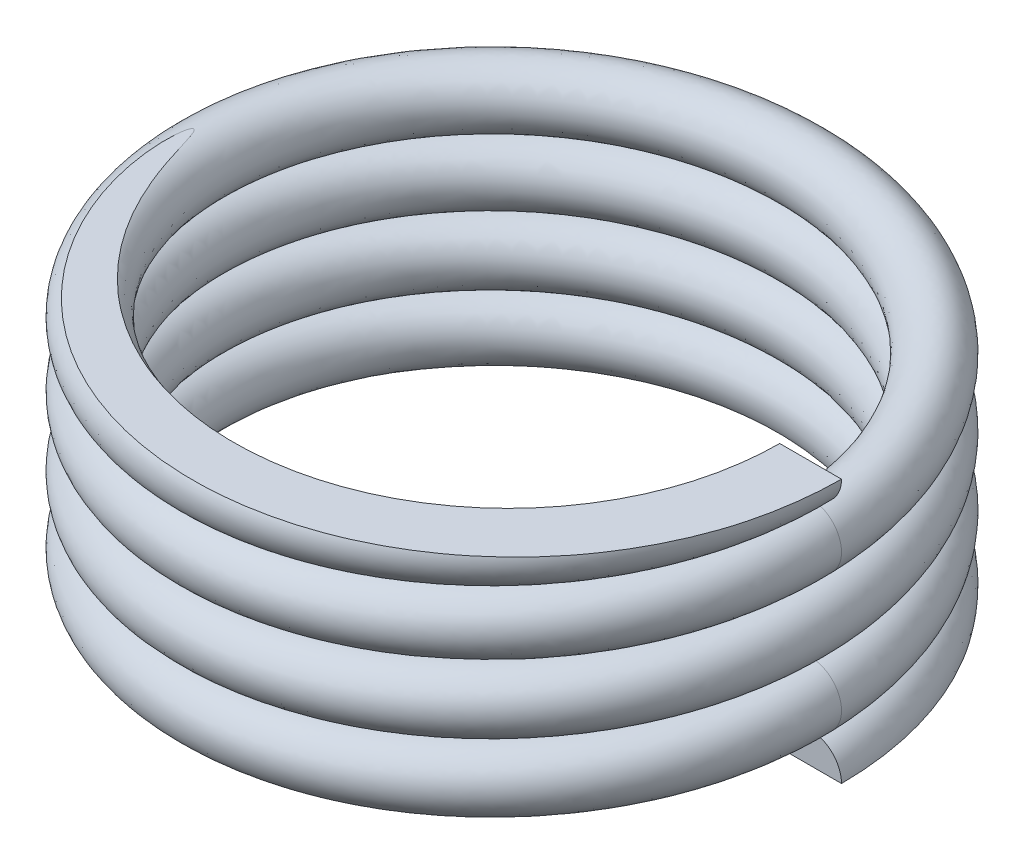
SolidWorks part; units mm, degrees
ref_plane "Front" through (0, 0, 0) normal (0, 0, 1) x (1, 0, 0)
ref_plane "Top" through (0, 0, 0) normal (0, 1, 0) x (1, 0, 0)
ref_plane "Right" through (0, 0, 0) normal (1, 0, 0) x (0, 0, -1)
sketch "Sketch1" plane through (0, 0, 0) normal (0, 0, 1) x (1, 0, 0)
  line L0 (5.5245, 4.8768) -> (5.5245, 4.3053) construction
  line L1 (0, 0) -> (5.5245, 0) construction
  line L2 (0, 0) -> (0, 4.8768) construction
  line L3 (0, 4.8768) -> (5.5245, 4.8768) construction
  line L4 (5.5245, 4.3053) -> (5.5245, 4.2799) construction
  line L5 (5.5245, 4.2799) -> (5.5245, 3.1369) construction
  line L6 (5.5245, 3.1369) -> (5.5245, 1.7399) construction
  line L7 (5.5245, 1.7399) -> (5.5245, 0.5969) construction
  line L8 (5.5245, 0.5969) -> (5.5245, 0.5715) construction
  line L9 (5.5245, 0.5715) -> (5.5245, 0) construction
  line L10 (5.5245, 0) -> (6.096, 0) construction
  line L11 (5.5245, 1.1684) -> (6.096, 1.1684) construction
  line L12 (5.5245, 4.8768) -> (6.096, 4.8768) construction
  line L13 (5.5245, 4.8768) -> (5.5245, 5.4483) construction
  line L14 (5.5245, 0) -> (5.5245, -0.5715) construction
  circle A0 centre (5.5245, 4.8768) radius 0.5715 construction
  circle A1 centre (5.5245, 3.7084) radius 0.5715 construction
  circle A2 centre (5.5245, 1.1684) radius 0.5715
  circle A3 centre (5.5245, 0) radius 0.5715 construction
  dimension "Wire Dia" = 1.143
  dimension "D3" = 2.54
  dimension "D4" = 1.1684
  dimension "D1" = 0.0254
  dimension "Spring-OD" = 12.192
  dimension "Overall Height" = 4.8768
ref_plane "Plane1" through (0, 1.1684, 0) normal (0, 1, 0) x (-1, 0, 0)
ref_plane "Plane2" through (0, 3.7084, 0) normal (0, 1, 0) x (-1, 0, 0)
sketch "Sketch2" plane through (0, 1.1684, 0) normal (0, 1, 0) x (-1, 0, 0)
  circle A0 centre (0, 0) radius 6.096
curve "Helix1" pitch 1.27 height 2.54 turns 2
sketch "Sketch3" plane through (0, 1.1684, 0) normal (0, 1, 0) x (-1, 0, 0)
  circle A0 centre (0, 0) radius 6.096 construction
  circle A1 centre (0, 0) radius 6.096
curve "Helix2" pitch 1.1684 height 1.1684 turns 1
sketch "Sketch4" plane through (0, 0, 0) normal (0, 0, 1) x (1, 0, 0)
  circle A0 centre (5.5245, 0) radius 0.5715 construction
  circle A1 centre (5.5245, 0) radius 0.5715
sketch "Sketch5" plane through (0, 3.7084, 0) normal (0, 1, 0) x (-1, 0, 0)
  circle A0 centre (0, 0) radius 6.096 construction
  circle A1 centre (0, 0) radius 6.096
curve "Helix3" pitch 1.1684 height 1.1684 turns 1
curve "CompCurve1"
sweep "Sweep1" add profiles "Sketch4" path "CompCurve1"
sketch "Sketch6" plane through (0, 0, 0) normal (0, 0, 1) x (1, 0, 0)
  line L0 (0, 0) -> (0, 4.8768) construction
  line L1 (-6.096, 4.8768) -> (6.096, 4.8768)
  line L2 (-6.096, -12.192) -> (-6.096, 0)
  line L3 (-6.096, 17.0688) -> (6.096, 17.0688)
  line L4 (6.096, 4.8768) -> (6.096, 17.0688)
  line L5 (-6.096, 0) -> (6.096, 0)
  line L7 (-6.096, -12.192) -> (6.096, -12.192)
  line L8 (6.096, 0) -> (6.096, -12.192)
  line L9 (0, 0) -> (0, 4.8768) construction
  line L10 (-6.096, 17.0688) -> (-6.096, 4.8768)
extrude "Extrude1" cut sketch "Sketch6" against normal through all and the other way through all
equation "\"D3@Helix1\"=\"D3@Sketch1\""
equation "\"D3@Helix2\"=\"D4@Sketch1\""
equation "\"D3@Helix3\"=\"D4@Sketch1\""
